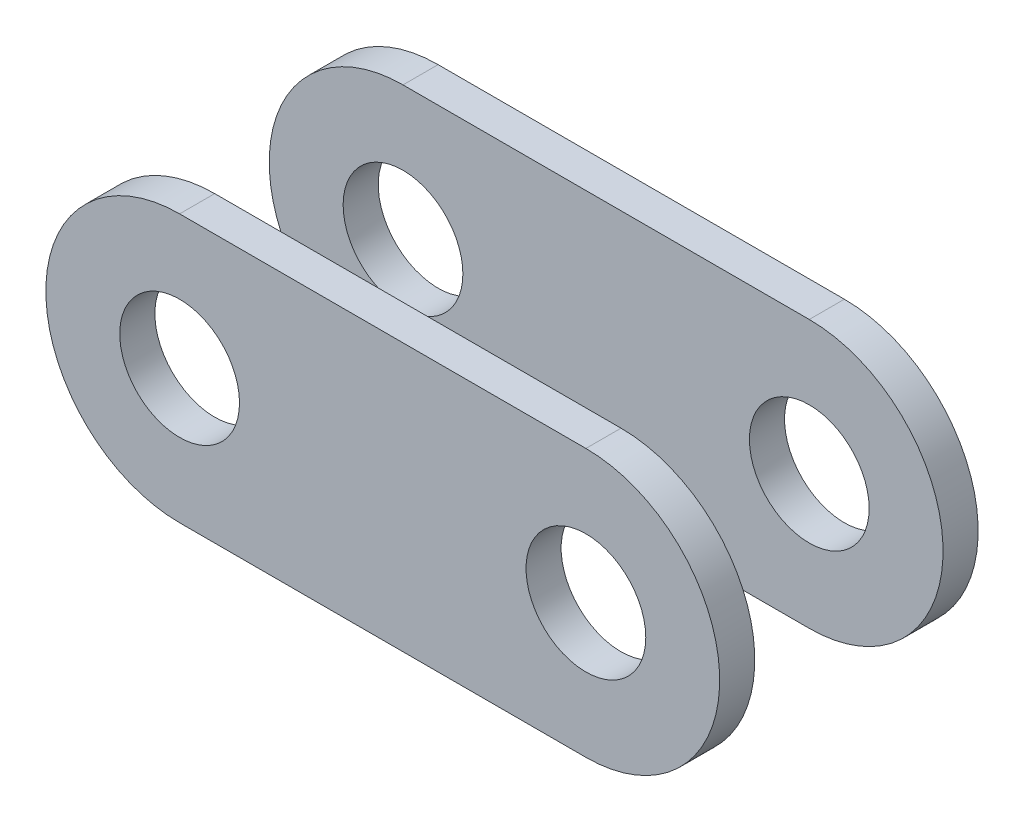
SolidWorks part; units mm, degrees
ref_plane "Front Plane" through (0, 0, 0) normal (0, 0, 1) x (1, 0, 0)
ref_plane "Top Plane" through (0, 0, 0) normal (0, 1, 0) x (1, 0, 0)
ref_plane "Right Plane" through (0, 0, 0) normal (1, 0, 0) x (0, 0, -1)
sketch "Sketch2" plane through (0, 0, 0) normal (0, 0, 1) x (1, 0, 0)
  line L0 (-9.4658, 0) -> (3.031, 0) construction
  line L1 (55, 0) -> (-55, 0) construction
  line L2 (-9.4658, 4.1148) -> (3.031, 4.1148)
  line L3 (-9.4658, -4.1148) -> (3.031, -4.1148)
  arc A0 (-9.4658, 4.1148) -> (-9.4658, -4.1148) centre (-9.4658, 0) ccw
  arc A1 (3.031, -4.1148) -> (3.031, 4.1148) centre (3.031, 0) ccw
  circle A2 centre (-9.4658, 0) radius 1.8415
  circle A3 centre (3.031, 0) radius 1.8415
  point P5 (-3.2174, 0)
  dimension "D1" = 3.683
  dimension "D2" = 3.683
  dimension "D3" = 12.4968
  dimension "D4" = 8.2296
extrude "Boss-Extrude1" add sketch "Sketch2" along normal blind 3.9751 and the other way blind 3.9751
sketch "Sketch3" plane through (0, 4.1148, 0) normal (0, 1, 0) x (1, 0, 0)
  line L0 (-13.5806, 3.9751) -> (-13.5806, -3.9751) construction
  line L1 (-13.5806, 2.8956) -> (7.1458, 2.8956)
  line L2 (-13.5806, 2.8956) -> (-13.5806, -2.8956)
  line L3 (-13.5806, -2.8956) -> (7.1458, -2.8956)
  line L4 (7.1458, 2.8956) -> (7.1458, -2.8956)
  line L5 (7.1458, -3.9751) -> (7.1458, 3.9751) construction
  line L6 (3.031, -3.9751) -> (-9.4658, -3.9751) construction
  dimension "D1" = 5.7912
  dimension "D2" = 1.0795
extrude "Cut-Extrude1" cut sketch "Sketch3" against normal through all
sketch "Sketch6" [suppressed] plane through (0, 4.1148, 0) normal (0, 1, 0) x (1, 0, 0)
  line L0 (-13.5806, 3.9751) -> (-13.5806, -3.9751) construction
  line L1 (-13.5806, 1.6891) -> (7.1458, 1.6891)
  line L2 (-13.5806, 1.6891) -> (-13.5806, -1.6891)
  line L3 (-13.5806, -1.6891) -> (7.1458, -1.6891)
  line L4 (7.1458, 1.6891) -> (7.1458, -1.6891)
  line L5 (7.1458, -3.9751) -> (7.1458, 3.9751) construction
  line L6 (3.031, 3.9751) -> (-9.4658, 3.9751) construction
  line L7 (3.031, -3.9751) -> (-9.4658, -3.9751) construction
  dimension "D1" = 2.286
  dimension "D2" = 2.286
extrude "Cut-Extrude2" [suppressed] cut sketch "Sketch6" against normal through all
sketch "Sketch7" [suppressed] plane through (0, 4.1148, 0) normal (0, 1, 0) x (1, 0, 0)
  line L0 (-13.5806, 3.9751) -> (-13.5806, 1.6891) construction
  line L1 (7.1458, 3.9751) -> (-13.5806, 3.9751)
  line L2 (7.1458, 3.9751) -> (7.1458, 2.8321)
  line L3 (7.1458, 2.8321) -> (-13.5806, 2.8321)
  line L4 (-13.5806, 3.9751) -> (-13.5806, 2.8321)
extrude "Cut-Extrude3" [suppressed] cut sketch "Sketch7" against normal through all
sketch "Sketch8" [suppressed] plane through (0, 4.1148, 0) normal (0, 1, 0) x (1, 0, 0)
  line L0 (-13.5806, -1.6891) -> (-13.5806, -3.9751) construction
  line L1 (7.1458, -3.9751) -> (-13.5806, -3.9751)
  line L2 (7.1458, -3.9751) -> (7.1458, -2.8321)
  line L3 (7.1458, -2.8321) -> (-13.5806, -2.8321)
  line L4 (-13.5806, -3.9751) -> (-13.5806, -2.8321)
  dimension "D1" = 1.143
extrude "Cut-Extrude4" [suppressed] cut sketch "Sketch8" against normal through all
equation "\"D1@Sketch2\"= \"D2@Sketch2\""
equation "\"D2@Sketch6\"= \"D1@Sketch6\""
